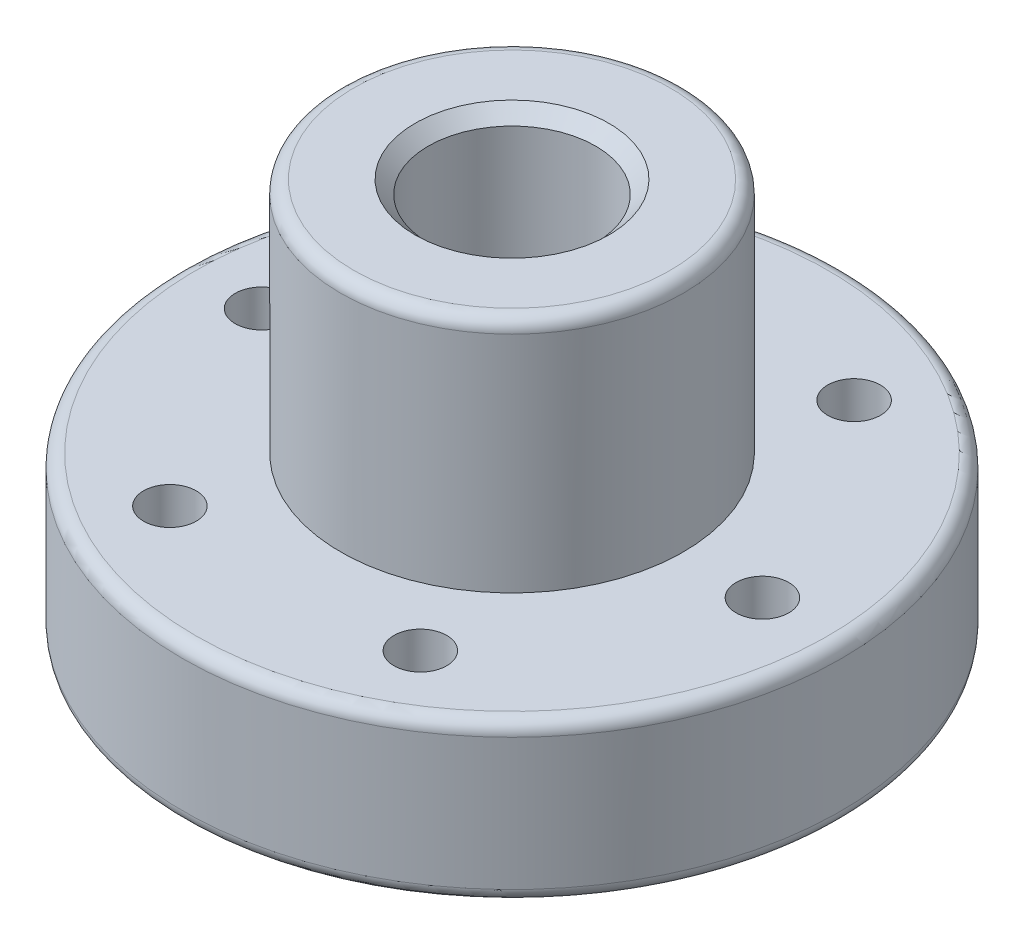
SolidWorks part; units mm, degrees
material "AISI 1035 Acier (SS)"
ref_plane "Plan de face" through (0, 0, 0) normal (0, 0, 1) x (1, 0, 0)
ref_plane "Plan de dessus" through (0, 0, 0) normal (0, 1, 0) x (1, 0, 0)
ref_plane "Plan de droite" through (0, 0, 0) normal (1, 0, 0) x (0, 0, -1)
sketch "Esquisse1" plane through (0, 0, 0) normal (0, 0, 1) x (1, 0, 0)
  line L0 (6.5, 15) -> (6.5, 6)
  line L1 (6.5, 6) -> (12.5, 6)
  line L2 (12.5, 6) -> (12.5, 0)
  line L9 (6.5, 15) -> (3.175, 15)
  line L10 (3.175, 15) -> (3.175, 0)
  line L11 (12.5, 0) -> (3.175, 0)
  line L12 (0, 0) -> (0, 15) construction
  dimension "D1" = 12.5
  dimension "D2" = 6
  dimension "D3" = 15
  dimension "D4" = 3.175
  dimension "D5" = 6
  dimension "D6" = 9.325
revolve "Révolution2" add sketch "Esquisse1" angle 360 about L12
sketch "Esquisse3" plane through (0, 6, 0) normal (0, 1, 0) x (1, 0, 0)
  line L0 (0, 0) -> (9.5, 0) construction
  circle A0 centre (9.5, 0) radius 1
  circle A2 centre (0, 0) radius 12.5 construction
  circle A3 centre (0, 0) radius 6.5 construction
  point P7 (6.5, 0)
  point P8 (12.5, 0)
  point P19 (0, 0)
  point P23 (0, -4.027)
  point P24 (0.0457, -3.8672)
  dimension "D1" = 2
  dimension "D3" = 3
  dimension "D2" = 3
extrude "Enlèv. mat.-Extru.1" cut sketch "Esquisse3" against normal through all
pattern_circular "Répétition circulaire1" count 6 over 360 about axis through (0, 0, 0) along (0, -1, 0) of "Enlèv. mat.-Extru.1"
fillet "Congé1" radius 0.5 3 edges at (0, 15, -6.5) (0, 0, -12.5) (0, 6, -12.5)
chamfer "Chanfrein1" distance 0.5 angle 45 2 edges at (0, 0, -3.175) (0, 15, -3.175)
sketch "Esquisse8" [suppressed] plane through (0, -5.2608, 0) normal (0, 1, 0) x (1, 0, 0)
  circle A0 centre (8, 0) radius 0.8
  circle A4 centre (0, -8) radius 0.8
  circle A5 centre (-8, 0) radius 0.8
  circle A6 centre (0, 8) radius 0.8
  point P12 (0, 0)
  dimension "D1" = 1.6
  dimension "D3" = 4
  dimension "D2" = 8
extrude "Enlèv. mat.-Extru.2" [suppressed] cut sketch "Esquisse8" against normal through all
